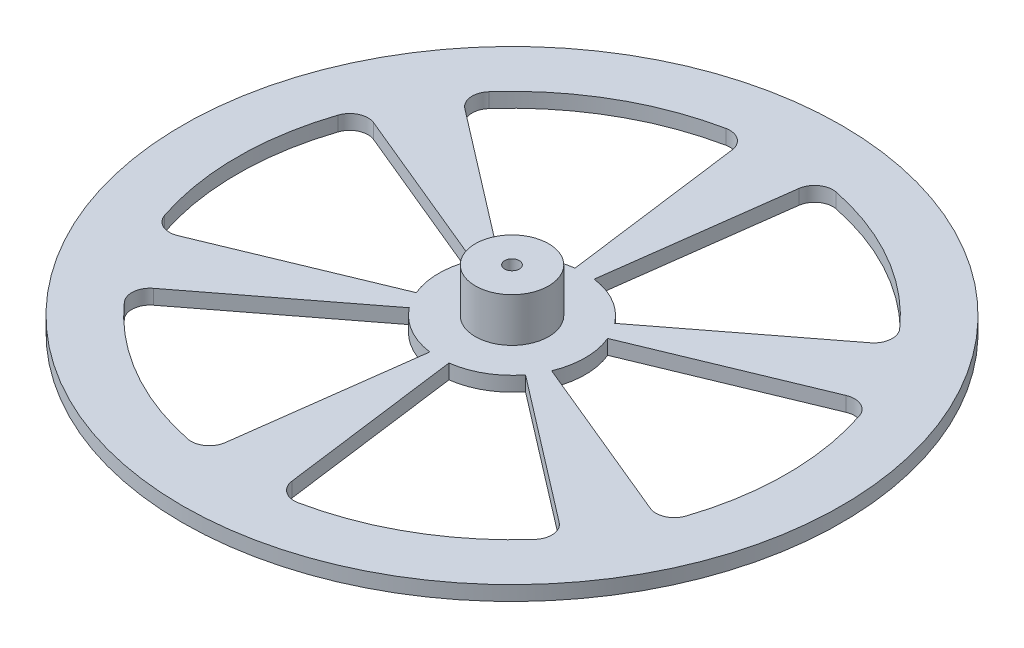
SolidWorks part; units mm, degrees
material "6061 合金"
ref_plane "前视基准面" through (0, 0, 0) normal (0, 0, 1) x (1, 0, 0)
ref_plane "上视基准面" through (0, 0, 0) normal (0, 1, 0) x (1, 0, 0)
ref_plane "右视基准面" through (0, 0, 0) normal (1, 0, 0) x (0, 0, -1)
other "Configuration Table"
sketch "草图1" plane through (0, 0, 0) normal (0, 1, 0) x (1, 0, 0)
  circle A0 centre (0, 0) radius 90
  dimension "D1" = 180
extrude "凸台-拉伸1" add sketch "草图1" along normal blind 4
sketch "草图2" plane through (0, 4, 0) normal (0, 1, 0) x (1, 0, 0)
  line L0 (0, 20) -> (0, 75)
  line L1 (-17.3205, 10) -> (-64.9519, 37.5)
  line L2 (-2.6105, 19.8289) -> (-9.7895, 74.3584)
  line L3 (-15.8671, 12.1752) -> (-59.5015, 45.6571)
  circle A0 centre (0, 0) radius 20
  circle A1 centre (0, 0) radius 75
  dimension "D1" = 40
  dimension "D2" = 60
  dimension "D3" = 7.5
  dimension "D4" = 7.5
ref_axis "基准轴1" through (0, 4, 0) along (0, 1, 0)
extrude "切除-拉伸1" cut sketch "草图2" against normal through all contours L2 A1 L3 A0 region at (-25.7301, 4, -44.5658)
pattern_circular "阵列(圆周)1" count 6 over 360 about axis through (0, 4, 0) along (0, 1, 0) of "切除-拉伸1"
sketch "草图6" plane through (0, 4, 0) normal (0, 1, 0) x (1, 0, 0)
  circle A0 centre (0, 0) radius 10
extrude "凸台-拉伸2" add sketch "草图6" along normal blind 12
sketch "草图7" plane through (0, 16, 0) normal (0, 1, 0) x (1, 0, 0)
  circle A0 centre (0, 0) radius 2
extrude "切除-拉伸2" cut sketch "草图7" against normal blind 12
sketch "草图8" plane through (0, 0, 0) normal (0, -1, 0) x (1, 0, 0)
  point P0 (0, 0)
fillet "圆角1" radius 5 1 edges at (9.7895, 2, 74.3584)
fillet "圆角2" radius 5 11 edges at (-59.5015, 2, 45.6571) (-9.7895, 2, 74.3584) (-69.291, 2, 28.7013) (-69.291, 2, -28.7013) (-9.7895, 2, -74.3584) (-59.5015, 2, -45.6571) (9.7895, 2, -74.3584) (59.5015, 2, -45.6571) (69.291, 2, -28.7013) (69.291, 2, 28.7013) (59.5015, 2, 45.6571)
sketch "草图9" plane through (0, 0, 0) normal (1, 0, 0) x (0, 0, -1)
  line L0 (10, 16) -> (-10, 16) construction
  circle A0 centre (0, 11) radius 2
  dimension "D1" = 5
extrude "切除-拉伸3" cut sketch "草图9" against normal blind 10
